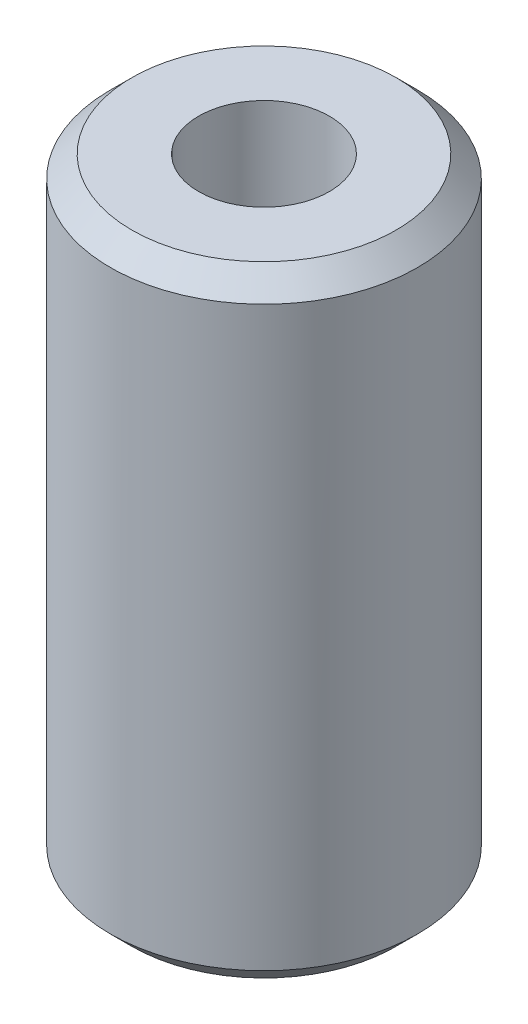
SolidWorks part; units mm, degrees
ref_plane "Front Plane" through (0, 0, 0) normal (0, 0, 1) x (1, 0, 0)
ref_plane "Top Plane" through (0, 0, 0) normal (0, 1, 0) x (1, 0, 0)
ref_plane "Right Plane" through (0, 0, 0) normal (1, 0, 0) x (0, 0, -1)
sketch "Sketch1" plane through (0, 0, 0) normal (0, 1, 0) x (1, 0, 0)
  circle A0 centre (0, 0) radius 27.5
  dimension "SHAFT_OD" = 55
extrude "Boss-Extrude1" add sketch "Sketch1" along normal blind 110.9831
sketch "Sketch2" plane through (0, 0, 0) normal (0, 1, 0) x (1, 0, 0)
  circle A0 centre (0, 0) radius 11.7007
  dimension "BORE_D" = 23.4014
extrude "Cut-Extrude1" cut sketch "Sketch2" along normal through all
chamfer "Chamfer1" distance 3.8608 angle 45 2 edges at (0, 110.9831, 27.5) (0, 0, 27.5)
